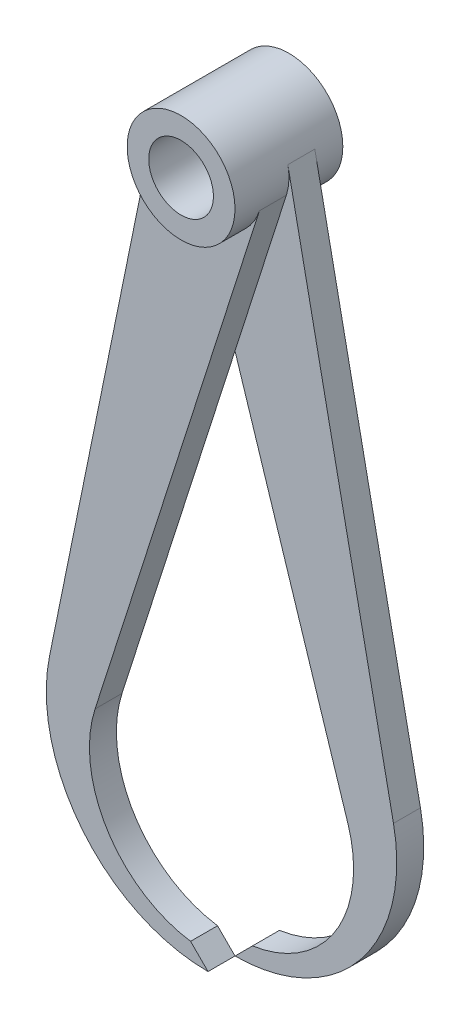
SolidWorks part; units mm, degrees
ref_plane "Front Plane" through (0, 0, 0) normal (0, 0, 1) x (1, 0, 0)
ref_plane "Top Plane" through (0, 0, 0) normal (0, 1, 0) x (1, 0, 0)
ref_plane "Right Plane" through (0, 0, 0) normal (1, 0, 0) x (0, 0, -1)
sketch "Sketch1" plane through (0, 0, 0) normal (0, 0, 1) x (1, 0, 0)
  line L0 (0, 0) -> (0, 50000) construction
  line L1 (0, 0) -> (50000, 0) construction
  line L2 (-29.3939, 11) -> (-9.798, 107)
  line L3 (29.3939, 11) -> (9.798, 107)
  line L4 (-20.9534, 6.7048) -> (9.5243, 101.9524)
  line L5 (20.9534, 6.7048) -> (-9.5243, 101.9524)
  line L6 (0, -25) -> (3.2399, -21.7601)
  line L7 (0, -25) -> (-3.2399, -21.7601)
  arc A4 (3.2399, -21.7601) -> (-3.2399, -21.7601) centre (0, 0) ccw
  circle A5 centre (0, 5) radius 30
  circle A6 centre (0, 105) radius 6
  circle A7 centre (0, 105) radius 10
  dimension "D1" = 44
  dimension "D2" = 5
  dimension "D3" = 60
  dimension "D4" = 12
  dimension "D5" = 20
  dimension "D6" = 100
  dimension "D7" = 90
extrude "Boss-Extrude1" add sketch "Sketch1" along normal mid plane 20 contours A7 A6 region at (0, 114.7172, 0)
extrude "Boss-Extrude2" add sketch "Sketch1<3>" along normal blind 5 contours L4 A5 L7 A4 | A7 L2 A5 L4 L5 | A7 L5 L4 region at (-23.0942, 23.1207, 0) region at (-12.8647, 59.9513, 0) region at (0, 88.366, 0)
sketch "Sketch1<3>" plane through (0, 0, 0) normal (0, 0, 1) x (1, 0, 0) same geometry as "Sketch1"
extrude "Boss-Extrude9" add sketch "Sketch1<8>" against normal blind 5 separate body contours A7 L4 L5 A5 L3 | A5 L5 A4 L6 | A7 L5 L4 region at (2.0762, -23.8363, 0) region at (12.8647, 59.9513, 0) region at (0, 88.366, 0)
sketch "Sketch1<8>" plane through (0, 0, 0) normal (0, 0, 1) x (1, 0, 0) same geometry as "Sketch1"
